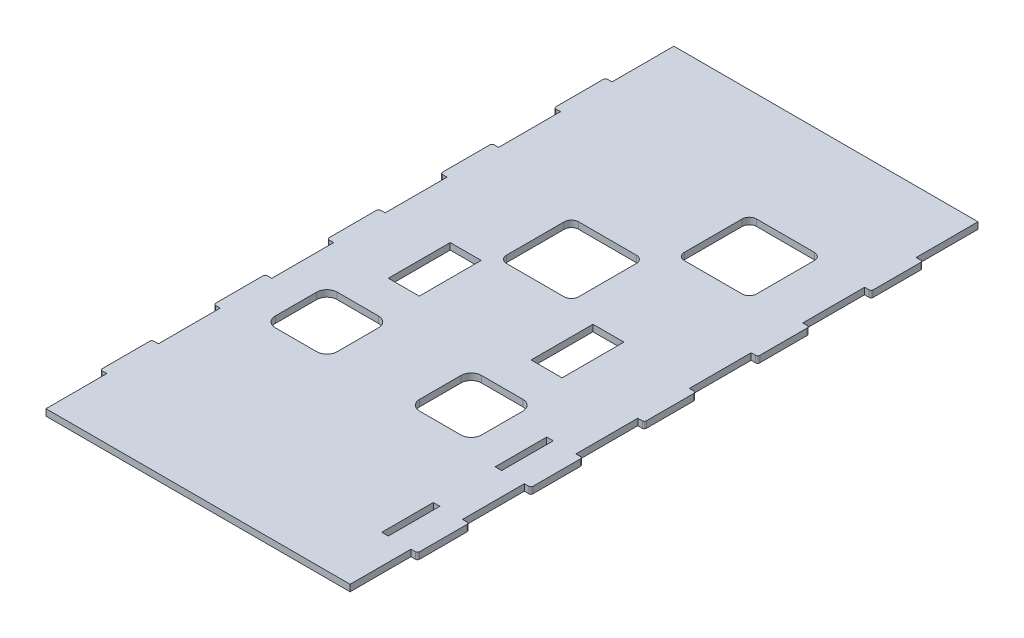
SolidWorks part; units mm, degrees
material "Beech"
ref_plane "Front Plane" through (0, 0, 0) normal (0, 0, 1) x (1, 0, 0)
ref_plane "Top Plane" through (0, 0, 0) normal (0, 1, 0) x (1, 0, 0)
ref_plane "Right Plane" through (0, 0, 0) normal (1, 0, 0) x (0, 0, -1)
sketch "Sketch1" plane through (0, 0, 0) normal (0, 1, 0) x (1, 0, 0)
  line L1 (0, 0) -> (295, 0)
  line L2 (0, 0) -> (0, 59)
  line L3 (0, 609) -> (295, 609)
  line L4 (295, 0) -> (295, 59)
  line L5 (0, 59) -> (-6.35, 59)
  line L7 (0, 109) -> (-6.35, 109)
  line L8 (-6.35, 59) -> (-6.35, 109)
  line L9 (0, 169) -> (-6.35, 169)
  line L10 (-6.35, 169) -> (-6.35, 219)
  line L11 (0, 219) -> (-6.35, 219)
  line L13 (0, 279) -> (-6.35, 279)
  line L14 (-6.35, 279) -> (-6.35, 329)
  line L15 (0, 329) -> (-6.35, 329)
  line L17 (0, 389) -> (-6.35, 389)
  line L18 (-6.35, 389) -> (-6.35, 439)
  line L19 (0, 439) -> (-6.35, 439)
  line L21 (0, 499) -> (-6.35, 499)
  line L22 (-6.35, 499) -> (-6.35, 549)
  line L23 (0, 549) -> (-6.35, 549)
  line L25 (295, 59) -> (301.35, 59)
  line L27 (295, 109) -> (301.35, 109)
  line L28 (301.35, 59) -> (301.35, 109)
  line L29 (295, 169) -> (301.35, 169)
  line L30 (301.35, 169) -> (301.35, 219)
  line L31 (295, 219) -> (301.35, 219)
  line L33 (295, 279) -> (301.35, 279)
  line L34 (301.35, 279) -> (301.35, 329)
  line L35 (295, 329) -> (301.35, 329)
  line L37 (295, 389) -> (301.35, 389)
  line L38 (301.35, 389) -> (301.35, 439)
  line L39 (295, 439) -> (301.35, 439)
  line L41 (295, 499) -> (301.35, 499)
  line L42 (301.35, 499) -> (301.35, 549)
  line L43 (295, 549) -> (301.35, 549)
  line L44 (0, 549) -> (0, 609)
  line L46 (0, 329) -> (0, 389)
  line L49 (0, 219) -> (0, 279)
  line L50 (0, 109) -> (0, 169)
  line L51 (295, 109) -> (295, 169)
  line L52 (295, 219) -> (295, 279)
  line L53 (295, 329) -> (295, 389)
  line L54 (295, 439) -> (295, 499)
  line L55 (295, 549) -> (295, 609)
  line L56 (0, 439) -> (0, 499)
  dimension "D1" = 609
  dimension "D2" = 295
  dimension "D3" = 6.35
  dimension "D4" = 50
  dimension "D5" = 59
  dimension "D7" = 60
  dimension "D8" = 50
  dimension "D9" = 6.35
  dimension "D11" = 59
  dimension "D12" = 60
  dimension "D6" = 5
  dimension "D10" = 5
extrude "Boss-Extrude1" add sketch "Sketch1" along normal blind 6.35
fillet "Fillet1" radius 2 20 edges at (301.35, 3.175, -549) (301.35, 3.175, -499) (301.35, 3.175, -439) (301.35, 3.175, -389) (301.35, 3.175, -329) (301.35, 3.175, -279) (301.35, 3.175, -219) (301.35, 3.175, -169) (301.35, 3.175, -109) (301.35, 3.175, -59) (-6.35, 3.175, -59) (-6.35, 3.175, -109) (-6.35, 3.175, -169) (-6.35, 3.175, -219) (-6.35, 3.175, -279) (-6.35, 3.175, -329) (-6.35, 3.175, -389) (-6.35, 3.175, -439) (-6.35, 3.175, -499) (-6.35, 3.175, -549)
sketch "Sketch2" plane through (0, 6.35, 0) normal (0, 1, 0) x (1, 0, 0)
  line L0 (266.65, 0) -> (266.65, 100) construction
  line L1 (0, 0) -> (295, 0) construction
  line L2 (0, 609) -> (0, 0) construction
  line L3 (295, 609) -> (295, 0) construction
  line L4 (0, 150) -> (266.65, 100) construction
  line L5 (266.65, 169) -> (266.65, 219)
  line L6 (266.65, 59) -> (273, 59)
  line L7 (266.65, 59) -> (266.65, 109)
  line L8 (266.65, 109) -> (273, 109)
  line L9 (273, 59) -> (273, 109)
  line L10 (266.65, 169) -> (273, 169)
  line L11 (273, 169) -> (273, 219)
  line L12 (266.65, 219) -> (273, 219)
  line L13 (0, 84.2124) -> (266.65, 84) construction
  line L14 (101.3481, 415.2724) -> (157.3481, 415.2724)
  line L15 (94.3481, 408.2724) -> (94.3481, 352.2724)
  line L16 (101.3481, 345.2724) -> (157.3481, 345.2724)
  line L17 (164.3481, 408.2724) -> (164.3481, 352.2724)
  line L18 (185.2335, 503.9695) -> (241.2335, 503.9695)
  line L19 (178.2335, 496.9695) -> (178.2335, 440.9695)
  line L20 (185.2335, 433.9695) -> (241.2335, 433.9695)
  line L21 (248.2335, 496.9695) -> (248.2335, 440.9695)
  line L22 (43.325, 239.1432) -> (83.325, 239.1432)
  line L23 (33.325, 229.1432) -> (33.325, 189.1432)
  line L24 (43.325, 179.1432) -> (83.325, 179.1432)
  line L25 (93.325, 229.1432) -> (93.325, 189.1432)
  line L26 (33.325, 239.1432) -> (93.325, 179.1432) construction
  line L27 (33.325, 179.1432) -> (93.325, 239.1432) construction
  line L32 (133.325, 0) -> (133.325, 609) construction
  line L33 (295, 609) -> (0, 609) construction
  line L34 (56.474, 335.5741) -> (86.474, 335.5741)
  line L35 (56.474, 335.5741) -> (56.474, 275.5741)
  line L36 (56.474, 275.5741) -> (86.474, 275.5741)
  line L37 (86.474, 335.5741) -> (86.474, 275.5741)
  line L38 (194.3557, 336.1934) -> (224.3557, 336.1934)
  line L39 (194.3557, 336.1934) -> (194.3557, 276.1934)
  line L40 (194.3557, 276.1934) -> (224.3557, 276.1934)
  line L41 (224.3557, 336.1934) -> (224.3557, 276.1934)
  line L42 (233.325, 179.1432) -> (173.325, 239.1432) construction
  line L43 (233.325, 239.1432) -> (173.325, 179.1432) construction
  line L44 (173.325, 229.1432) -> (173.325, 189.1432)
  line L45 (223.325, 179.1432) -> (183.325, 179.1432)
  line L46 (233.325, 229.1432) -> (233.325, 189.1432)
  line L47 (223.325, 239.1432) -> (183.325, 239.1432)
  arc A0 (94.3481, 352.2724) -> (101.3481, 345.2724) centre (101.3481, 352.2724) ccw
  arc A1 (157.3481, 345.2724) -> (164.3481, 352.2724) centre (157.3481, 352.2724) ccw
  arc A2 (157.3481, 415.2724) -> (164.3481, 408.2724) centre (157.3481, 408.2724) cw
  arc A3 (101.3481, 415.2724) -> (94.3481, 408.2724) centre (101.3481, 408.2724) ccw
  arc A4 (178.2335, 440.9695) -> (185.2335, 433.9695) centre (185.2335, 440.9695) ccw
  arc A5 (241.2335, 433.9695) -> (248.2335, 440.9695) centre (241.2335, 440.9695) ccw
  arc A6 (241.2335, 503.9695) -> (248.2335, 496.9695) centre (241.2335, 496.9695) cw
  arc A7 (185.2335, 503.9695) -> (178.2335, 496.9695) centre (185.2335, 496.9695) ccw
  arc A8 (33.325, 189.1432) -> (43.325, 179.1432) centre (43.325, 189.1432) ccw
  arc A9 (83.325, 179.1432) -> (93.325, 189.1432) centre (83.325, 189.1432) ccw
  arc A10 (83.325, 239.1432) -> (93.325, 229.1432) centre (83.325, 229.1432) cw
  arc A11 (43.325, 239.1432) -> (33.325, 229.1432) centre (43.325, 229.1432) ccw
  arc A16 (223.325, 239.1432) -> (233.325, 229.1432) centre (223.325, 229.1432) cw
  arc A17 (183.325, 239.1432) -> (173.325, 229.1432) centre (183.325, 229.1432) ccw
  arc A18 (183.325, 179.1432) -> (173.325, 189.1432) centre (183.325, 189.1432) cw
  arc A19 (233.325, 189.1432) -> (223.325, 179.1432) centre (223.325, 189.1432) cw
  point P33 (164.3481, 345.2724)
  point P36 (164.3481, 415.2724)
  point P39 (94.3481, 415.2724)
  point P42 (178.2335, 433.9695)
  point P47 (248.2335, 503.9695)
  point P50 (178.2335, 503.9695)
  point P51 (63.325, 209.1432)
  point P74 (133.325, 84.1062)
  point P99 (203.325, 209.1432)
  dimension "D10" = 7
  dimension "D11" = 7
  dimension "D16" = 10
  dimension "D17" = 70
  dimension "D1" = 100
  dimension "D2" = 150
  dimension "D3" = 6.35
  dimension "D4" = 50
  dimension "D6" = 70
  dimension "D7" = 70
  dimension "D8" = 70
  dimension "D9" = 70
  dimension "D12" = 60
  dimension "D13" = 60
  dimension "D14" = 22
  dimension "D15" = 59
  dimension "D18" = 30
  dimension "D19" = 60
  dimension "D20" = 30
  dimension "D21" = 60
  dimension "D5" = 2
extrude "Cut-Extrude1" cut sketch "Sketch2" against normal blind 6.35
